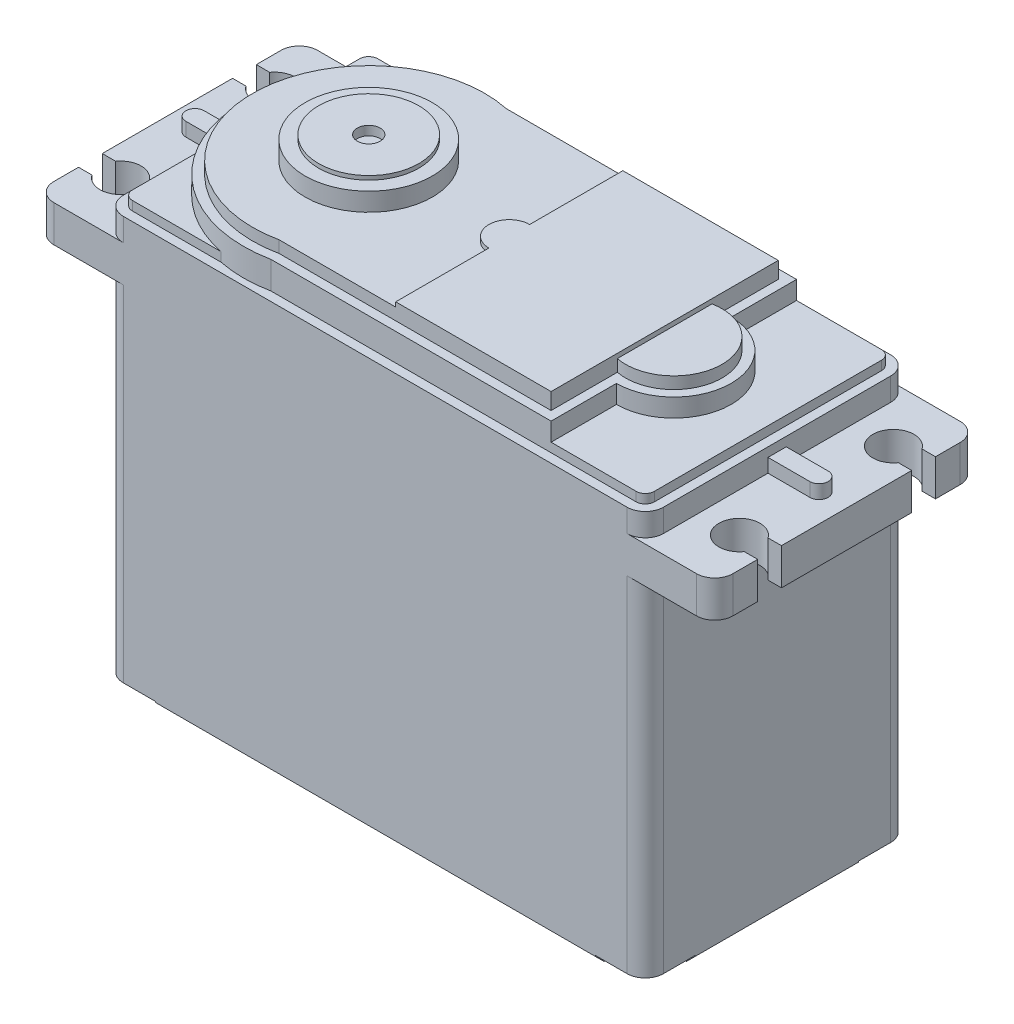
SolidWorks part; units mm, degrees
ref_plane "Alzado" through (0, 0, 0) normal (0, 0, 1) x (1, 0, 0)
ref_plane "Planta" through (0, 0, 0) normal (0, 1, 0) x (1, 0, 0)
ref_plane "Vista lateral" through (0, 0, 0) normal (1, 0, 0) x (0, 0, -1)
sketch "Croquis1" plane through (0, 0, 0) normal (0, 1, 0) x (1, 0, 0)
  line L1 (-29.55, -14.425) -> (29.55, -14.425)
  line L2 (-29.55, -14.425) -> (-29.55, 14.425)
  line L3 (-29.55, 14.425) -> (29.55, 14.425)
  line L4 (29.55, -14.425) -> (29.55, 14.425)
  line L5 (-29.55, -14.425) -> (29.55, 14.425) construction
  line L6 (-29.55, 14.425) -> (29.55, -14.425) construction
  point P0 (0, 0)
  dimension "D1" = 59.1
  dimension "D2" = 28.85
extrude "Saliente-Extruir1" add sketch "Croquis1" along normal mid plane 45.3
sketch "Croquis2" plane through (0, -22.65, 0) normal (0, -1, 0) x (1, 0, 0)
  line L0 (0, 0) -> (0, -50000) construction
  line L1 (29.55, 14.425) -> (24.05, 14.425)
  line L2 (29.55, 14.425) -> (29.55, 8.925)
  line L3 (29.55, 8.925) -> (26.05, 8.925)
  line L4 (24.05, 14.425) -> (24.05, 10.925)
  line L5 (0, 0) -> (50000, 0) construction
  line L6 (-29.55, 14.425) -> (-29.55, 8.925)
  line L7 (-29.55, 14.425) -> (-24.05, 14.425)
  line L8 (-24.05, 14.425) -> (-24.05, 10.925)
  line L9 (-29.55, 8.925) -> (-26.05, 8.925)
  line L10 (0, 0) -> (-50000, 0) construction
  line L11 (24.05, -14.425) -> (24.05, -10.925)
  line L12 (29.55, -8.925) -> (26.05, -8.925)
  line L13 (29.55, -14.425) -> (29.55, -8.925)
  line L14 (29.55, -14.425) -> (24.05, -14.425)
  line L15 (-24.05, -14.425) -> (-24.05, -10.925)
  line L16 (-29.55, -14.425) -> (-24.05, -14.425)
  line L17 (-29.55, -14.425) -> (-29.55, -8.925)
  line L18 (-29.55, -8.925) -> (-26.05, -8.925)
  arc A0 (26.05, -8.925) -> (24.05, -10.925) centre (26.05, -10.925) ccw
  arc A1 (-24.05, -10.925) -> (-26.05, -8.925) centre (-26.05, -10.925) ccw
  arc A2 (-26.05, 8.925) -> (-24.05, 10.925) centre (-26.05, 10.925) ccw
  arc A3 (26.05, 8.925) -> (24.05, 10.925) centre (26.05, 10.925) cw
  point P26 (24.05, -8.925)
  point P29 (-24.05, -8.925)
  point P32 (-24.05, 8.925)
  point P35 (24.05, 8.925)
  dimension "D3" = 2
  dimension "D1" = 5.5
  dimension "D2" = 5.5
extrude "Cortar-Extruir1" cut sketch "Croquis2" against normal blind 1.1
chamfer "Chaflán1" distance 1 angle 45 4 edges at (-29.55, -22.65, 0) (0, -22.65, -14.425) (29.55, -22.65, 0) (0, -22.65, 14.425)
fillet "Redondeo1" radius 2 4 edges at (29.55, 0.55, 14.425) (29.55, 0.55, -14.425) (-29.55, 0.55, -14.425) (-29.55, 0.55, 14.425)
ref_plane "Plano1" through (0, 16.15, 0) normal (0, 1, 0) x (1, 0, 0)
sketch "Croquis3" plane through (0, 16.15, 0) normal (0, 1, 0) x (1, 0, 0)
  line L0 (29.55, -12.425) -> (29.55, 12.425) construction
  line L1 (27.55, 14.425) -> (37.15, 14.425)
  line L2 (-37.15, 0) -> (-50000, 0) construction
  line L3 (27.55, -14.425) -> (37.15, -14.425)
  line L4 (37.15, 14.425) -> (37.15, 9.725)
  line L5 (0, 0) -> (0, -50000) construction
  line L6 (35.6, 7.125) -> (37.15, 7.125)
  line L7 (37.15, 7.125) -> (37.15, -7.125)
  line L8 (35.6, 9.725) -> (37.15, 9.725)
  line L9 (0, 0) -> (27.55, 0) construction
  line L10 (35.6, -9.725) -> (37.15, -9.725)
  line L11 (35.6, -7.125) -> (37.15, -7.125)
  line L12 (37.15, -9.725) -> (37.15, -14.425)
  line L13 (37.15, 0) -> (50000, 0) construction
  line L14 (0, 0) -> (-27.55, 0) construction
  line L15 (-37.15, -9.725) -> (-37.15, -14.425)
  line L16 (-35.6, -7.125) -> (-37.15, -7.125)
  line L17 (-35.6, -9.725) -> (-37.15, -9.725)
  line L18 (-35.6, 9.725) -> (-37.15, 9.725)
  line L19 (-37.15, 7.125) -> (-37.15, -7.125)
  line L20 (-35.6, 7.125) -> (-37.15, 7.125)
  line L21 (-37.15, 14.425) -> (-37.15, 9.725)
  line L22 (-27.55, -14.425) -> (-37.15, -14.425)
  line L23 (-27.55, 14.425) -> (-37.15, 14.425)
  line L24 (29.55, 12.425) -> (29.55, -12.425)
  line L25 (-29.55, 12.425) -> (-29.55, -12.425)
  line L26 (35.6, 9.725) -> (35.6, 7.125)
  line L27 (35.6, -7.125) -> (35.6, -9.725)
  line L28 (-35.6, 9.725) -> (-35.6, 7.125)
  line L29 (-35.6, -7.125) -> (-35.6, -9.725)
  arc A4 (-27.55, 14.425) -> (-29.55, 12.425) centre (-27.55, 12.425) ccw
  arc A5 (-27.55, -14.425) -> (-29.55, -12.425) centre (-27.55, -12.425) cw
  arc A6 (27.55, -14.425) -> (29.55, -12.425) centre (27.55, -12.425) ccw
  arc A7 (27.55, 14.425) -> (29.55, 12.425) centre (27.55, 12.425) cw
  point P11 (36.03, 8.425)
  point P23 (36.03, -8.425)
  point P44 (-36.03, -8.425)
  point P45 (-36.03, 8.425)
  dimension "D2" = 7.6
extrude "Saliente-Extruir2" add sketch "Croquis3" along normal blind 4
fillet "Redondeo2" radius 2 4 edges at (-37.15, 18.15, 14.425) (-37.15, 18.15, -14.425) (37.15, 18.15, -14.425) (37.15, 18.15, 14.425)
sketch "Croquis4" plane through (0, 20.15, 0) normal (0, 1, 0) x (1, 0, 0)
  line L0 (0, 0) -> (35.1, 0) construction
  line L1 (29.55, 12.425) -> (29.55, -12.425) construction
  line L2 (34.1322, -1) -> (29.55, -1)
  line L3 (0, 0) -> (0, -50000) construction
  line L4 (34.1322, 1) -> (29.55, 1)
  line L5 (29.55, -1) -> (29.55, 1)
  line L6 (34.668, -0.8443) -> (29.55, 1) construction
  line L7 (34.668, 0.8443) -> (29.55, -1) construction
  line L8 (-34.668, 0.8443) -> (-29.55, -1) construction
  line L9 (-29.55, -1) -> (-29.55, 1)
  line L10 (-34.1322, 1) -> (-29.55, 1)
  line L11 (-34.1322, -1) -> (-29.55, -1)
  arc A0 (34.1322, 1) -> (34.1322, -1) centre (34.1322, 0) cw
  arc A1 (-34.1322, 1) -> (-34.1322, -1) centre (-34.1322, 0) ccw
  point P3 (32.325, 0)
  point P21 (-32.325, 0)
extrude "Saliente-Extruir3" add sketch "Croquis4" along normal blind 1.5
sketch "Croquis5" plane through (0, 22.65, 0) normal (0, 1, 0) x (1, 0, 0)
  line L8 (-27.55, -13.425) -> (27.55, -13.425)
  line L9 (28.55, -12.425) -> (28.55, 12.425)
  line L10 (27.55, 13.425) -> (-27.55, 13.425)
  line L11 (-28.55, 12.425) -> (-28.55, -12.425)
  line L12 (-27.55, -13.425) -> (27.55, -13.425)
  line L13 (28.55, -12.425) -> (28.55, 12.425)
  line L14 (27.55, 13.425) -> (-27.55, 13.425)
  line L15 (-28.55, 12.425) -> (-28.55, -12.425)
  arc A8 (27.55, -13.425) -> (28.55, -12.425) centre (27.55, -12.425) ccw
  arc A9 (28.55, 12.425) -> (27.55, 13.425) centre (27.55, 12.425) ccw
  arc A10 (-27.55, 13.425) -> (-28.55, 12.425) centre (-27.55, 12.425) ccw
  arc A11 (-28.55, -12.425) -> (-27.55, -13.425) centre (-27.55, -12.425) ccw
  arc A12 (27.55, -13.425) -> (28.55, -12.425) centre (27.55, -12.425) ccw
  arc A13 (28.55, 12.425) -> (27.55, 13.425) centre (27.55, 12.425) ccw
  arc A14 (-27.55, 13.425) -> (-28.55, 12.425) centre (-27.55, 12.425) ccw
  arc A15 (-28.55, -12.425) -> (-27.55, -13.425) centre (-27.55, -12.425) ccw
  dimension "D1" = 1
extrude "Saliente-Extruir4" add sketch "Croquis5" along normal blind 1
sketch "Croquis6" plane through (0, 22.65, 0) normal (0, 1, 0) x (1, 0, 0)
  line L0 (-1024.7876, 0) -> (-28.55, 0) construction
  line L1 (27.55, 13.425) -> (-27.55, 13.425) construction
  line L2 (-12.3938, 13.425) -> (18.25, 13.425)
  line L3 (18.25, -6.275) -> (18.25, -13.425)
  line L4 (-12.3938, -13.425) -> (18.25, -13.425)
  line L5 (18.25, 13.425) -> (18.25, 6.275)
  line L6 (-27.55, -13.425) -> (27.55, -13.425) construction
  line L7 (29.55, -12.425) -> (29.55, 12.425) construction
  line L8 (24.525, 0) -> (50000, 0) construction
  arc A0 (18.25, 6.275) -> (18.25, -6.275) centre (18.25, 0) cw
  arc A1 (-12.3938, 13.425) -> (-12.3938, -13.425) centre (-15.125, 0) ccw
  dimension "D1" = 27.4
  dimension "D3" = 6.275
  dimension "D2" = 11.3
extrude "Saliente-Extruir5" add sketch "Croquis6" along normal blind 3
sketch "Croquis7" plane through (0, 25.65, 0) normal (0, 1, 0) x (1, 0, 0)
  line L8 (17.25, 5.1793) -> (17.25, 12.425)
  line L9 (17.25, 12.425) -> (-12.4964, 12.425)
  line L10 (-12.4964, -12.425) -> (17.25, -12.425)
  line L11 (17.25, -12.425) -> (17.25, -5.1793)
  line L12 (17.25, 5.1793) -> (17.25, 12.425)
  line L13 (17.25, 12.425) -> (-12.4964, 12.425)
  line L14 (-12.4964, -12.425) -> (17.25, -12.425)
  line L15 (17.25, -12.425) -> (17.25, -5.1793)
  arc A5 (17.25, -5.1793) -> (17.25, 5.1793) centre (18.25, 0) ccw
  arc A6 (-12.4964, 12.425) -> (-12.4964, -12.425) centre (-15.125, 0) ccw
  arc A7 (17.25, -5.1793) -> (17.25, 5.1793) centre (18.25, 0) ccw
  arc A8 (-12.4964, 12.425) -> (-12.4964, -12.425) centre (-15.125, 0) ccw
  dimension "D1" = 1
extrude "Saliente-Extruir6" add sketch "Croquis7" along normal blind 1.3
sketch "Croquis8" plane through (0, 26.95, 0) normal (0, 1, 0) x (1, 0, 0)
  line L0 (0, 0) -> (50000, 0) construction
  circle A0 centre (-15.125, 0) radius 6.96
  dimension "D1" = 13.92
extrude "Saliente-Extruir7" add sketch "Croquis8" along normal blind 2
sketch "Croquis9" plane through (0, 28.95, 0) normal (0, 1, 0) x (1, 0, 0)
  circle A0 centre (-15.125, 0) radius 5.485
  dimension "D1" = 10.97
extrude "Saliente-Extruir8" add sketch "Croquis9" along normal blind 0.44
sketch "Croquis10" plane through (0, 29.39, 0) normal (0, 1, 0) x (1, 0, 0)
  circle A0 centre (-15.125, 0) radius 1.25
  dimension "D1" = 2.5
extrude "Cortar-Extruir2" cut sketch "Croquis10" against normal blind 1
hole_wizard "Taladro de margen para M1.61" positions "Croquis12" profile "Croquis11" hole size "M1.6" standard "As"
sketch "Croquis12" plane through (0, -21.55, 0) normal (0, -1, 0) x (-1, 0, 0)
  line L0 (-29.55, 12.425) -> (-29.55, 8.925) construction
  line L1 (-24.05, 14.425) -> (-27.55, 14.425) construction
  point P0 (-27.05, 11.925)
  dimension "D1" = 2.5
  dimension "D2" = 2.5
sketch "Croquis11" plane through (27.05, -21.55, -11.925) normal (1, 0, 0) x (0, 0, -1)
  line L0 (0, 0) -> (0, 5.5408)
  line L1 (0, 5.5408) -> (0.9, 5)
  line L2 (0.9, 5) -> (0.9, 0)
  line L5 (0.9, 0) -> (0, 0)
  line L10 (0, 5.5408) -> (-0.9, 5) construction
  line L11 (0, -6.35) -> (0, 107.95) construction
  dimension "Diámetro de taladro" = 1.8
  dimension "Profundidad de taladro" = 5
  dimension "Ángulo de perforador" = 118
mirror "Simetría1" about plane through (0, 0, 0) normal (0, 0, 1) of "Taladro de margen para M1.61"
mirror "Simetría2" about plane through (0, 0, 0) normal (1, 0, 0) of "Simetría1"
ref_axis "Eje1" through (35.6, 20.15, -8.425) along (-1, 0, 0)
hole_wizard "Taladro de margen para #81" positions "Croquis14" profile "Croquis13" hole size "#8" standard "Ansi Inch" end condition up to next
sketch "Croquis14" plane through (0, 20.15, 0) normal (0, 1, 0) x (1, 0, 0)
  line L0 (37.15, 9.725) -> (37.15, 12.425) construction
  line L1 (35.6, 8.425) -> (-35.6, 8.425) construction
  line L2 (-37.15, 12.425) -> (-37.15, 9.725) construction
  line L3 (-37.15, 7.125) -> (-37.15, -7.125) construction
  point P0 (33.85, 8.425)
  point P7 (33.85, -8.425)
  point P9 (-33.85, 8.425)
  point P11 (-33.85, -8.425)
  dimension "D1" = 3.3
  dimension "D2" = 0
  dimension "D3" = 3.3
  dimension "D4" = 3.3
sketch "Croquis13" plane through (33.85, 20.15, -8.425) normal (1, 0, 0) x (0, 0, 1)
  line L0 (0, 0) -> (0, 4)
  line L1 (0, 4) -> (2.2479, 4)
  line L2 (2.2479, 4) -> (2.2479, 0)
  line L5 (2.2479, 0) -> (0, 0)
  line L11 (0, -6.35) -> (0, 107.95) construction
  dimension "Diámetro de taladro hasta el siguiente" = 4.4958
  dimension "Profundidad de taladro hasta el siguiente" = 4
sketch "Croquis15" plane through (0, 26.95, 0) normal (0, 1, 0) x (1, 0, 0)
  line L0 (-12.4964, -12.425) -> (17.25, -12.425) construction
  line L1 (17.25, 12.425) -> (0.25, 12.425)
  line L2 (17.25, 12.425) -> (17.25, -12.425)
  line L3 (17.25, -12.425) -> (0.25, -12.425)
  line L4 (0.25, 12.425) -> (0.25, 2.23)
  line L5 (0.25, -2.23) -> (0.25, -12.425)
  arc A0 (0.25, 2.23) -> (0.25, -2.23) centre (0.25, 0) ccw
  dimension "D2" = 4.46
  dimension "D1" = 17
extrude "Saliente-Extruir9" add sketch "Croquis15" along normal blind 0.5
sketch "Croquis17" plane through (-29.55, 0, 0) normal (-1, 0, 0) x (0, 0, 1)
  line L0 (0, 0) -> (0, -50000) construction
  line L2 (8.925, -22.65) -> (-8.925, -22.65) construction
  line L3 (-3.62, -14.39) -> (3.62, -14.39)
  line L4 (-3.62, -14.39) -> (-3.62, -18.8)
  line L5 (-3.62, -18.8) -> (3.62, -18.8)
  line L6 (3.62, -14.39) -> (3.62, -18.8)
  line L7 (-3.62, -14.39) -> (3.62, -18.8) construction
  line L8 (-3.62, -18.8) -> (3.62, -14.39) construction
  point P2 (0, -16.595)
  dimension "D1" = 3.85
  dimension "D2" = 7.24
  dimension "D3" = 4.41
ref_plane "Plano4" through (-35.55, 0, 0) normal (-1, 0, 0) x (0, 0, 1)
sketch "Croquis18" plane through (-35.55, 0, 0) normal (-1, 0, 0) x (0, 0, 1)
  line L8 (3.12, -14.89) -> (-3.12, -14.89)
  line L9 (3.12, -18.3) -> (3.12, -14.89)
  line L10 (-3.12, -18.3) -> (3.12, -18.3)
  line L11 (-3.12, -14.89) -> (-3.12, -18.3)
  line L12 (3.12, -14.89) -> (-3.12, -14.89)
  line L13 (3.12, -18.3) -> (3.12, -14.89)
  line L14 (-3.12, -18.3) -> (3.12, -18.3)
  line L15 (-3.12, -14.89) -> (-3.12, -18.3)
  point P0 (0, -16.595)
  dimension "D1" = 0.5
loft "Recubrir1" add profiles "Croquis17", "Croquis18"
